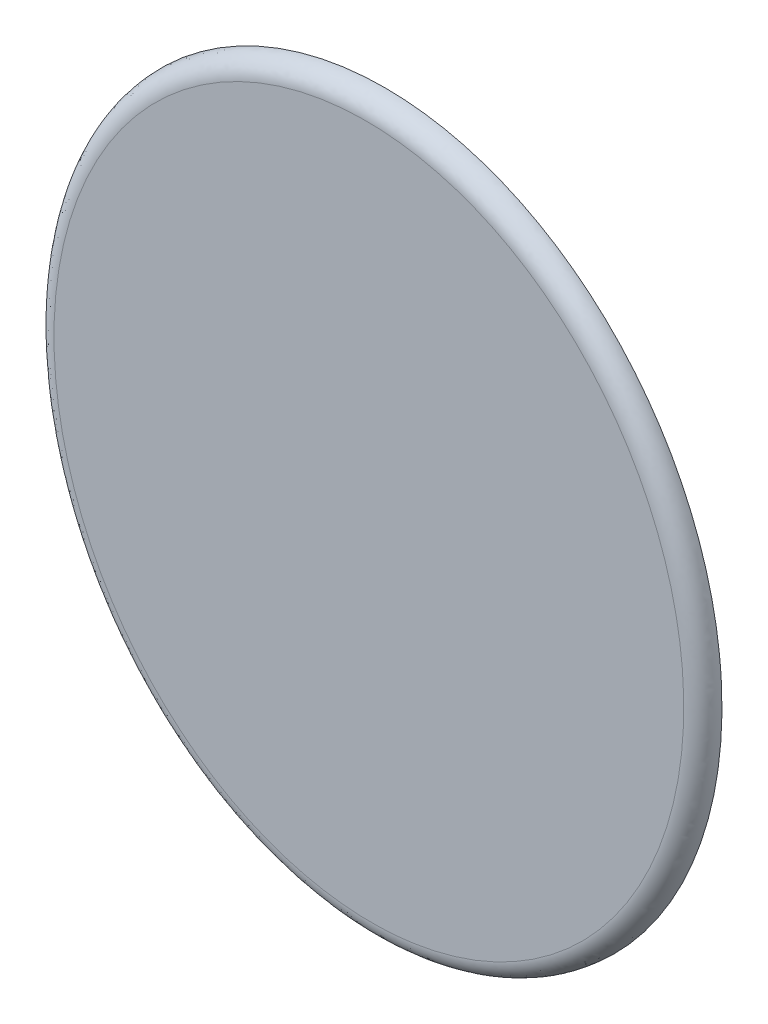
SolidWorks part; units mm, degrees
material "Acrylic (Medium-high impact)"
ref_plane "Front Plane" through (0, 0, 0) normal (0, 0, 1) x (1, 0, 0)
ref_plane "Top Plane" through (0, 0, 0) normal (0, 1, 0) x (1, 0, 0)
ref_plane "Right Plane" through (0, 0, 0) normal (1, 0, 0) x (0, 0, -1)
sketch "Sketch1" plane through (0, 0, 0) normal (0, 0, 1) x (1, 0, 0)
  ellipse E0 centre (0, 0) end of major axis (2.4802, -48.4876) minor radius 44.4247
extrude "Boss-Extrude1" add sketch "Sketch1" along normal blind 2.54 contours E0
fillet "Fillet3" radius 2.54 1 edges at (2.4802, -48.4876, 2.54)
